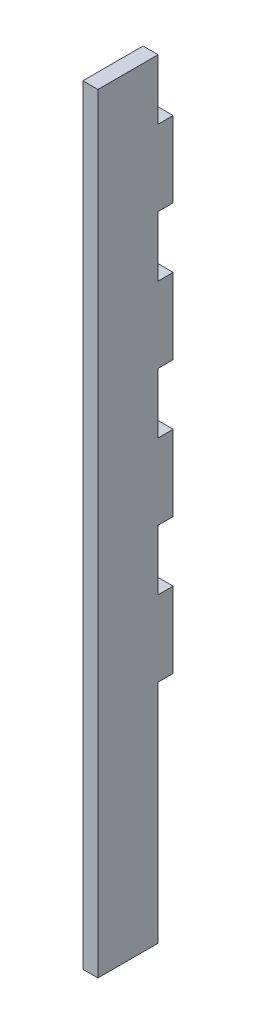
SolidWorks part; units mm, degrees
material "Acrylic (Medium-high impact)"
ref_plane "Front" through (0, 0, 0) normal (0, 0, 1) x (1, 0, 0)
ref_plane "Top" through (0, 0, 0) normal (0, 1, 0) x (1, 0, 0)
ref_plane "Right" through (0, 0, 0) normal (1, 0, 0) x (0, 0, -1)
sketch "Sketch1" plane through (0, 0, 0) normal (1, 0, 0) x (0, 0, -1)
  line L3 (-7.9375, -162.306) -> (7.9375, -162.306)
  line L69 (7.9375, 0) -> (7.9375, -162.306)
  line L70 (-7.9375, -162.306) -> (-7.9375, 0)
  line L71 (4.7625, -127.3048) -> (4.7625, -143.256)
  line L74 (6.35, -12.7) -> (6.35, -28.6512) construction
  line L75 (6.35, -41.3512) -> (6.35, -57.3024) construction
  line L76 (6.35, -70.0024) -> (6.35, -85.9536) construction
  line L77 (6.35, -98.6536) -> (6.35, -114.6048) construction
  line L82 (7.9375, 0) -> (-7.9375, 0)
  line L83 (7.9375, 0) -> (7.9375, -12.7)
  line L84 (7.9375, 0) -> (4.7625, 0)
  line L85 (4.7625, 0) -> (4.7625, -12.7)
  line L86 (7.9375, -12.7) -> (4.7625, -12.7)
  line L87 (7.9375, -28.6512) -> (7.9375, -41.3512)
  line L88 (7.9375, -28.6512) -> (4.7625, -28.6512)
  line L89 (4.7625, -28.6512) -> (4.7625, -41.3512)
  line L90 (7.9375, -41.3512) -> (4.7625, -41.3512)
  line L91 (7.9375, -57.3024) -> (7.9375, -70.0024)
  line L92 (7.9375, -57.3024) -> (4.7625, -57.3024)
  line L93 (4.7625, -57.3024) -> (4.7625, -70.0024)
  line L94 (7.9375, -70.0024) -> (4.7625, -70.0024)
  line L95 (7.9375, -85.9536) -> (7.9375, -98.6536)
  line L96 (7.9375, -85.9536) -> (4.7625, -85.9536)
  line L97 (4.7625, -85.9536) -> (4.7625, -98.6536)
  line L98 (7.9375, -98.6536) -> (4.7625, -98.6536)
  line L107 (6.35, -127.3048) -> (6.35, -143.256) construction
  line L108 (7.9375, -114.6048) -> (4.7625, -114.6048)
  line L109 (7.9375, -114.6048) -> (7.9375, -127.3048)
  line L110 (7.9375, -127.3048) -> (4.7625, -127.3048)
  line L111 (4.7625, -114.6048) -> (4.7625, -127.3048)
  line L113 (4.7625, -143.256) -> (7.9375, -143.256)
  line L114 (4.7625, -143.256) -> (4.7625, -155.956)
  line L115 (4.7625, -155.956) -> (7.9375, -155.956)
  line L116 (7.9375, -143.256) -> (7.9375, -155.956)
  line L117 (7.9375, -155.956) -> (4.7625, -155.956)
  line L118 (7.9375, -155.956) -> (7.9375, -162.306)
  line L119 (7.9375, -162.306) -> (4.7625, -162.306)
  line L120 (4.7625, -155.956) -> (4.7625, -162.306)
  point P4 (0, -162.306)
  point P44 (6.35, -143.256)
  dimension "D2" = 12.7
  dimension "D4" = 3.175
  dimension "D3" = 6.35
  dimension "D1" = 15.9512
  dimension "D5" = 12.7
extrude "Boss-Extrude1" add sketch "Sketch1" along normal blind 3.175 contours L120 L114 L71 L111 L108 L69 L98 L97 L96 L94 L93 L92 L90 L89 L88 L86 L85 L82 L70 L3
sketch "Sketch2" plane through (3.175, 0, 0) normal (1, 0, 0) x (0, 0, -1)
  line L6 (7.9375, -70.0024) -> (20.1295, -70.0024)
  line L7 (7.9375, -70.0024) -> (7.9375, -85.9536)
  line L8 (7.9375, -85.9536) -> (20.1295, -85.9536)
  line L9 (20.1295, -70.0024) -> (20.1295, -85.9536)
  line L11 (7.9375, -76.3905) -> (13.7795, -76.3905)
  line L12 (7.9375, -76.3905) -> (7.9375, -79.5655)
  line L13 (7.9375, -79.5655) -> (13.7795, -79.5655)
  line L14 (13.7795, -76.3905) -> (13.7795, -79.5655)
  line L31 (7.9375, -70.0024) -> (4.7625, -70.0024) construction
  point P22 (13.7795, -77.978)
  point P27 (20.1295, -77.978)
  dimension "D1" = 12.192
  dimension "D3" = 3.175
  dimension "D4" = 5.842
extrude "Boss-Extrude2" [suppressed] add sketch "Sketch2" against normal up to surface (2.9972 mm away) up to face at (0, -67.1525, -4.7625)
equation "\"bottomThickness\"= .25in"
equation "\"wallThickness\"= .125in"
equation "\"D4@Sketch1\"=\"wallThickness\""
equation "\"D3@Sketch1\"=\"bottomThickness\""
equation "\"D1@Boss-Extrude1\"=\"wallThickness\""
